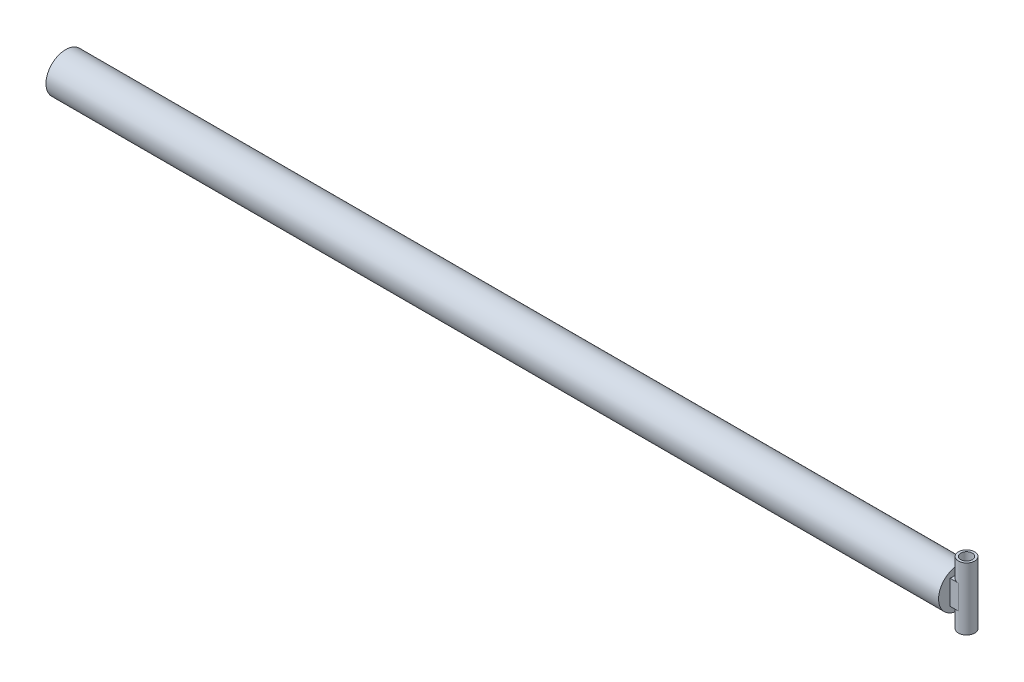
SolidWorks part; units mm, degrees
material "Plain Carbon Steel"
ref_plane "Front Plane" through (0, 0, 0) normal (0, 0, 1) x (1, 0, 0)
ref_plane "Top Plane" through (0, 0, 0) normal (0, 1, 0) x (1, 0, 0)
ref_plane "Right Plane" through (0, 0, 0) normal (1, 0, 0) x (0, 0, -1)
sketch "cilindar_Sketch2" plane through (0, 0, 0) normal (0, 1, 0) x (1, 0, 0)
  circle A0 centre (1966, 0) radius 35
  circle A1 centre (1966, 0) radius 25
  dimension "D2" = 70
  dimension "D3" = 50
  dimension "D1" = 1966
sketch "cilindar_Sketch1" plane through (0, 0, 0) normal (0, 1, 0) x (1, 0, 0)
  line L0 (-1930, 0) -> (1930, 0)
  line L1 (1930, 0) -> (1930, 75)
  line L2 (1930, 75) -> (1900, 75)
  line L3 (1900, 75) -> (1900, 85)
  line L4 (1900, 85) -> (-1900, 85)
  line L6 (-1900, 85) -> (-1900, 75)
  line L7 (-1900, 75) -> (-1930, 75)
  line L8 (-1930, 75) -> (-1930, 0)
  dimension "D1" = 85
  dimension "D3" = 30
  dimension "D2" = 3800
  dimension "D4" = 75
revolve "cilindar_Revolve1" add sketch "cilindar_Sketch1" angle 360 about L0 region at (0, 0, -42.4313)
shell "cilindar_Shell1" thickness 10 removed face at (-1930, 0, 75)
sketch "cilindar_Sketch3" plane through (0, 0, 0) normal (0, 1, 0) x (1, 0, 0)
  line L0 (-1900, 85) -> (-1900, -85) construction
  line L1 (-1900, 85) -> (-1900, -85) construction
  line L2 (-1930, 75) -> (-1930, -75) construction
  line L3 (-1930, 75) -> (-1930, -75) construction
  line L4 (-1930, 75) -> (-1900, 75)
  line L5 (-1900, 75) -> (-1900, 85)
  line L6 (-1900, 85) -> (-1930, 85)
  line L7 (-1930, 85) -> (-1930, 75)
ref_axis "cilindar_Axis1" through (1890, 0, 0) along (-1, 0, 0)
revolve "cilindar_Revolve2" add sketch "cilindar_Sketch3" angle 360 about axis through (1890, 0, 0) along (-1, 0, 0)
mirror "cilindar_Mirror2" about plane through (0, 0, 0) normal (1, 0, 0) of "cilindar_Revolve2"
extrude "cilindar_Boss-Extrude1" add sketch "cilindar_Sketch2" along normal blind 135 and the other way blind 135 separate body
sketch "cilindar_Sketch6" plane through (1930, 0, 0) normal (1, 0, 0) x (0, 0, -1)
  line L0 (-35, 135) -> (-35, -135) construction
  line L1 (35, -135) -> (35, 135) construction
  line L2 (-35, 135) -> (-35, -135) construction
  line L3 (35, -135) -> (35, 135) construction
  line L4 (35, 52.5) -> (35, -52.5)
  line L5 (-35, 52.5) -> (-35, -52.5) construction
  line L6 (35, 52.5) -> (-35, 52.5)
  line L7 (-35, -52.5) -> (35, 52.5) construction
  line L8 (35, -52.5) -> (-35, -52.5)
  line L9 (-35, 52.5) -> (-35, -52.5)
  dimension "D1" = 105
extrude "cilindar_Boss-Extrude7" add sketch "cilindar_Sketch6" along normal up to next
sketch "cilindar_Sketch7" plane through (-1930, 0, 0) normal (-1, 0, 0) x (0, 0, 1)
  circle A2 centre (0, 0) radius 18.75
  circle A3 centre (0, 0) radius 65 construction
  circle A4 centre (0, 0) radius 65
  dimension "D1" = 37.5
extrude "cilindar_Boss-Extrude8" add sketch "cilindar_Sketch7" against normal blind 10
equation "\"sirina_klipa\"= 150"
equation "\"debljina_klipa\"= 20"
equation "\"sirina_klipnjace\"= \"sirina_klipa\" / 4"
equation "\"duljina_klipnjace\"= 3800"
equation "\"r2_v\"= 70"
equation "\"r2_u\"= 50"
equation "\"r1_v\"= 70"
equation "\"r1_u\"= 50"
equation "\"l2\"= 310"
equation "\"l1\"= 270"
equation "\"sirina_cilindra\"= \"sirina_klipa\" + \"debljina_stijenke\" * 2"
equation "\"duljina_komore\"= 30"
equation "\"debljina_stijenke\"= 10"
equation "\"D3@cilindar_Sketch1\"= \"duljina_komore\""
equation "\"D4@cilindar_Sketch1\"=\"sirina_klipa\"/2"
equation "\"D1@cilindar_Sketch1\"=\"sirina_cilindra\"/2"
equation "\"D2@cilindar_Sketch1\"= \"duljina_cilindra\""
equation "\"D1@cilindar_Shell1\"=\"debljina_stijenke\""
equation "\"duljina_cilindra\"= \"duljina_klipnjace\" + \"debljina_klipa\" + \"debljina_stijenke\" - \"duljina_komore\""
equation "\"D1@cilindar_Sketch2\"=\"duljina_cilindra\"/2 + \"duljina_komore\" + \"r1_v\"/2 + 1"
equation "\"D2@cilindar_Sketch2\"=\"r1_v\""
equation "\"D3@cilindar_Sketch2\"=\"r1_u\""
equation "\"D1@cilindar_Sketch7\" = \"sirina_klipnjace\""
equation "\"D2@cilindar_Boss-Extrude1\"=\"l1\"/2"
equation "\"D1@cilindar_Boss-Extrude1\"=\"l1\"/2"
equation "\"D1@klip_Boss-Extrude1\"=\"debljina_klipa\""
equation "\"D1@klip_Sketch1\"=\"sirina_klipa\""
equation "\"D2@klip_Sketch3\"= \"duljina_klipnjace\" + \"r2_v\" / 2"
equation "\"D3@klip_Sketch3\" = \"r2_u\""
equation "\"D1@klip_Sketch3\"=\"r2_v\""
equation "\"D1@klip_Boss-Extrude3\"=\"l1\"/2"
equation "\"D2@klip_Boss-Extrude3\"=\"l1\"/2"
